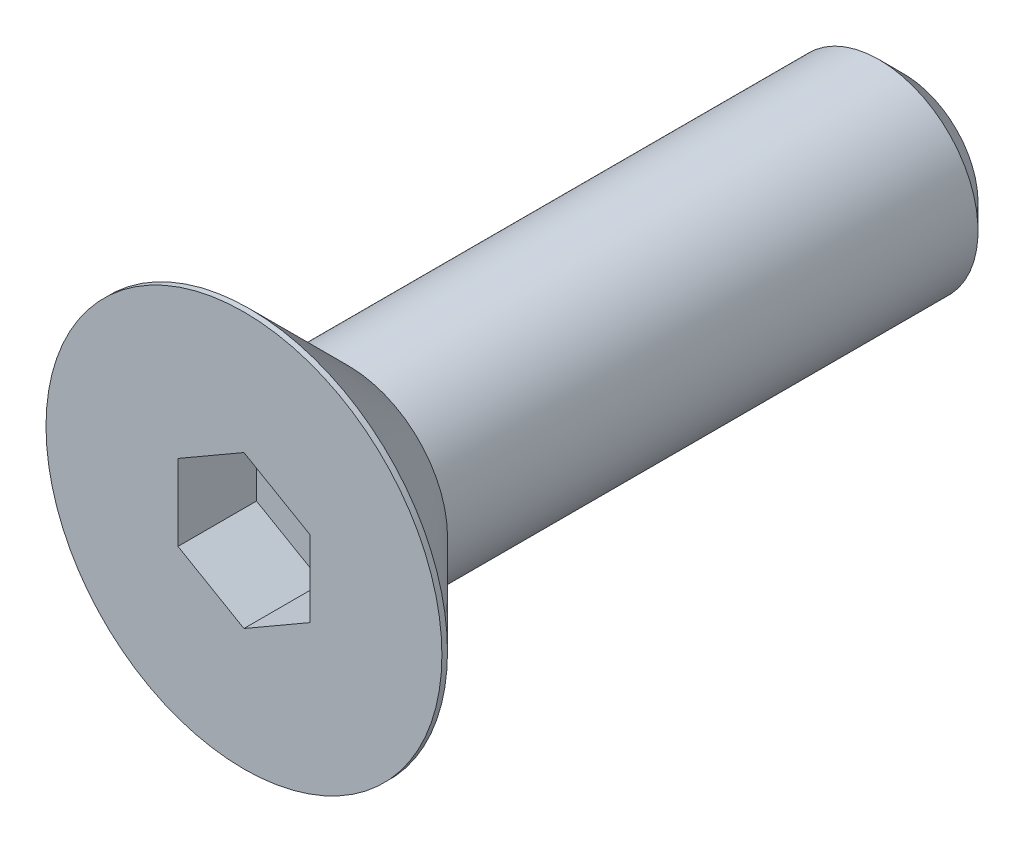
SolidWorks part; units mm, degrees
material "Chrome Stainless Steel"
ref_plane "Front" through (0, 0, 0) normal (0, 0, 1) x (1, 0, 0)
ref_plane "Top" through (0, 0, 0) normal (0, 1, 0) x (1, 0, 0)
ref_plane "Right" through (0, 0, 0) normal (1, 0, 0) x (0, 0, -1)
sketch "Sketch11" plane through (0, 0, 0) normal (1, 0, 0) x (0, 0, -1)
  line L0 (-5, 3) -> (5, 3) construction
  line L5 (-5, 3) -> (-5, -3) construction
  line L6 (5, 1.5) -> (5, -1.5) construction
  line L7 (-4.99, 1) -> (-4.99, -1) construction
  line L8 (4.9688, 1.5541) -> (5.4688, 1.5541) construction
  line L9 (5.4688, 1.5541) -> (5.2188, 1.1211) construction
  line L10 (5.2188, 1.1211) -> (4.9688, 1.5541) construction
  line L11 (5.1875, 1.1752) -> (5.25, 1.1752) construction
  line L12 (5.2188, 1.1752) -> (5.2188, 1.1211) construction
  line L13 (4.9844, 1.5271) -> (5.4531, 1.5271) construction
  line L14 (5.2188, 1.5541) -> (5.2188, 1.5) construction
  line L15 (5, 1.5) -> (5.4375, 1.5) construction
  line L17 (-4.915, 3) -> (-1.915, 0) construction
  line L18 (-1.915, 0) -> (-4.915, -3) construction
  point P3 (-3.3, 3)
  point P8 (0, 3)
  point P21 (5.2188, 1.5271)
  point P26 (-5, 0)
  point P28 (-4.99, 0)
  point P29 (5, 0)
  dimension "Length" = 10
  dimension "Head Diameter" = 6
  dimension "Thread Major Diameter" = 3
  dimension "Head Height" = 1.7
  dimension "Drive Size" = 2
  dimension "Thread Pitch" = 0.5
  dimension "D1" = 0.0625
  dimension "D2" = 0.01
  dimension "D3" = 0.085
  dimension "Countersink Angle" = 90
sketch "Sketch1" plane through (0, 0, 0) normal (1, 0, 0) x (0, 0, -1)
  line L2 (-3.3, 1.5) -> (5, 1.5)
  line L3 (5, 1.5) -> (5, 0)
  line L4 (-3.81, 1.5) -> (-3.81, 0)
  line L5 (-3.3, 1.5) -> (-3.81, 1.5)
  line L6 (-5, 3) -> (-5, -3) construction
  line L7 (5, 1.5) -> (5, -1.5) construction
  line L8 (-3.81, 0) -> (5, 0)
  dimension "D1" = 1.19
revolve "Revolve1" add sketch "Sketch1" angle 360 mid plane about L8
chamfer "Chamfer1" distance 0.375 angle 45 1 edges at (0, -1.5, -5)
sketch "Sketch7" plane through (0, 0, 0) normal (1, 0, 0) x (0, 0, -1)
  line L2 (-5, 3) -> (-4.915, 3)
  line L5 (-3.3, 1.385) -> (-3.3, 0)
  line L6 (-5, 3) -> (-5, 0)
  line L8 (-5, 3) -> (-5, -3) construction
  line L9 (-5, 0) -> (-3.3, 0)
  line L12 (-4.915, 3) -> (-3.3, 1.385)
  line L13 (-4.915, 3) -> (-1.915, 0) construction
revolve "Revolve2" add sketch "Sketch7" angle 360 mid plane about L9 region at (0, 1.1696, 4.2571)
ref_plane "Plane1" through (0, 0, 3.3) normal (0, 0, 1) x (1, 0, 0)
sketch "Sketch5" plane through (0, 0, 5) normal (0, 0, 1) x (1, 0, 0)
  line L1 (1, -0.5774) -> (1, 0.5774)
  line L2 (1, 0.5774) -> (0, 1.1547)
  line L3 (0, 1.1547) -> (-1, 0.5774)
  line L4 (-1, 0.5774) -> (-1, -0.5774)
  line L5 (-1, -0.5774) -> (0, -1.1547)
  line L6 (0, -1.1547) -> (1, -0.5774)
  circle A0 centre (0, 0) radius 1 construction
extrude "Cut-Extrude2" cut sketch "Sketch5" against normal blind 1.19
sketch "Sketch6" plane through (0, 0, 5) normal (0, 0, -1) x (-1, 0, 0)
  circle A0 centre (0, 0) radius 1.1547
extrude "Cut-Extrude3" [suppressed] cut sketch "Sketch6" along normal blind 1.19 draft 45
sketch "Sketch12" [suppressed] plane through (0, 0, -5) normal (0, 0, -1) x (-1, 0, 0)
  circle A0 centre (0, 0) radius 1.5 construction
  circle A1 centre (0, 0) radius 1.5
curve "Helix/Spiral1" [suppressed] pitch 0.5 height 10 turns 20
sketch "Sketch13" [suppressed] plane through (0, 0, 0) normal (1, 0, 0) x (0, 0, -1)
  line L0 (4.9844, 1.5271) -> (5.4531, 1.5271)
  line L1 (5.4531, 1.5271) -> (5.25, 1.1752)
  line L2 (5.25, 1.1752) -> (5.1875, 1.1752)
  line L3 (5.1875, 1.1752) -> (4.9844, 1.5271)
sweep "Cut-Sweep1" [suppressed] cut profiles "Sketch13" path "Helix/Spiral1"
combine bodies "Combine1" [suppressed] operation type add bodies to combine 113 127
equation "\"D1@Chamfer1\"=\"Thread Pitch@Sketch11\" * .75"
equation "\"D1@Cut-Extrude2\"= \"Head Height@Sketch11\" * .7"
equation "\"D1@Cut-Extrude3\" = \"D1@Cut-Extrude2\""
equation "\"D1@Sketch11\"=\"Thread Pitch@Sketch11\"/8"
equation "\"D3@Sketch11\"=\"Head Height@Sketch11\"*.05"
equation "\"D4@Helix/Spiral1\"=\"Thread Pitch@Sketch11\""
equation "\"D1@Sketch1\"=\"Head Height@Sketch11\"*.7"
equation "\"D3@Helix/Spiral1\"=\"Length@Sketch11\""
